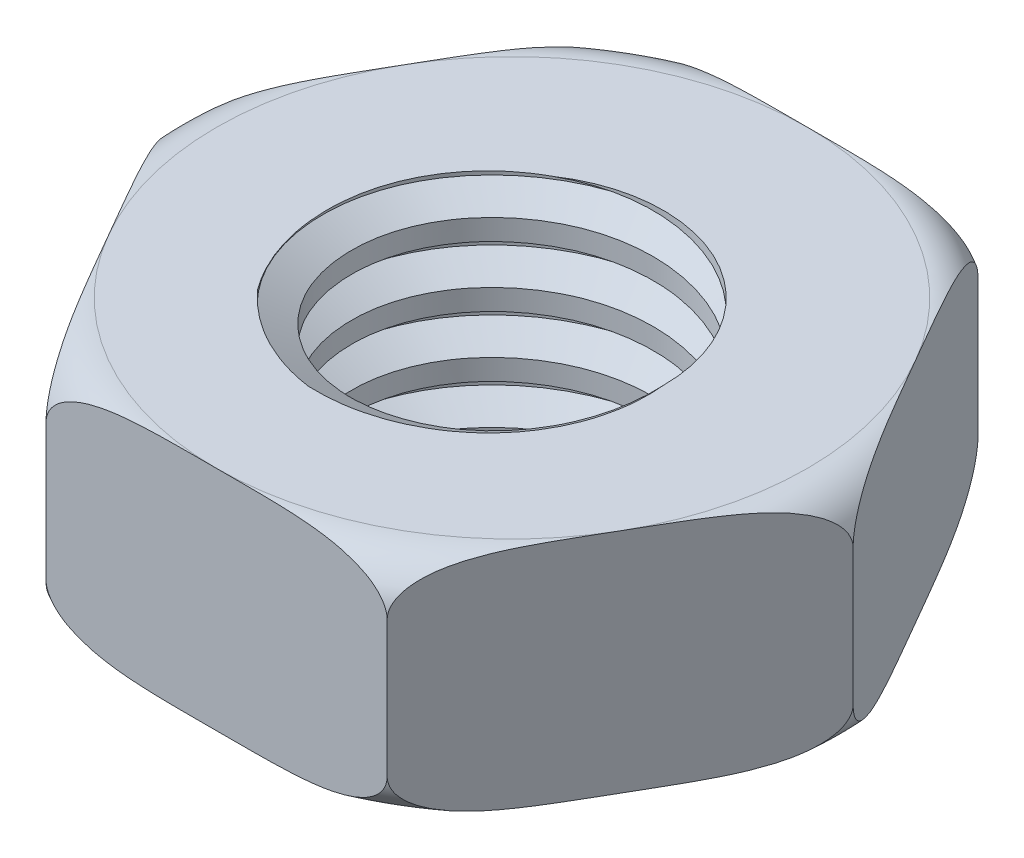
SolidWorks part; units mm, degrees
ref_plane "Front Plane" through (0, 0, 0) normal (0, 0, 1) x (1, 0, 0)
ref_plane "Top Plane" through (0, 0, 0) normal (0, 1, 0) x (1, 0, 0)
ref_plane "Right Plane" through (0, 0, 0) normal (1, 0, 0) x (0, 0, -1)
sketch "Sketch1" plane through (0, 0, 0) normal (0, 1, 0) x (1, 0, 0)
  line L1 (2.2517, 0) -> (1.1258, 1.95)
  line L2 (1.1258, 1.95) -> (-1.1258, 1.95)
  line L3 (-1.1258, 1.95) -> (-2.2517, 0)
  line L4 (-2.2517, 0) -> (-1.1258, -1.95)
  line L5 (-1.1258, -1.95) -> (1.1258, -1.95)
  line L6 (1.1258, -1.95) -> (2.2517, 0)
  circle A0 centre (0, 0) radius 1.95 construction
  circle A1 centre (0, 0) radius 1
  dimension "D2" = 2
  dimension "D1" = 3.9
extrude "Boss-Extrude1" add sketch "Sketch1" along normal mid plane 1.5
sketch "Sketch2" plane through (0, 0, 0) normal (0, 0, 1) x (1, 0, 0)
  line L0 (0, 0.75) -> (0, 0) construction
  line L3 (2.2517, 0.75) -> (2.2517, 0.4483)
  line L4 (1.1258, 0.75) -> (2.2517, 0.75) construction
  line L5 (2.2517, 0.75) -> (2.2517, -0.75) construction
  line L6 (1.1258, -0.75) -> (2.2517, -0.75) construction
  line L7 (1.95, -0.75) -> (2.2517, -0.75)
  line L8 (2.2517, -0.4483) -> (2.2517, -0.75)
  line L9 (2.2517, 0.75) -> (1.95, 0.75)
  line L10 (0, 0.75) -> (1.95, 0.75) construction
  arc A1 (2.2517, -0.4483) -> (1.95, -0.75) centre (1.95, -0.4483) cw
  arc A2 (1.95, 0.75) -> (2.2517, 0.4483) centre (1.95, 0.4483) cw
  point P1 (2.2517, 0.2825)
  dimension "D1" = 1.95
revolve "Cut-Revolve1" cut sketch "Sketch2" angle 360 about L0
thread "Thread1" pitch 0.35 start angle 0, offset 0, length 5, pitch 0.4, diameter 2
ref_plane "Plane1" through (1, 0.75, 0) normal (0, 0, 1) x (1, 0, 0)
sketch "Thread Profile1" plane through (1, 0.75, 0) normal (0, 0, 1) x (1, 0, 0)
  line L0 (0, 0) -> (0, 0.35) construction
  line L1 (0, 0) -> (0.1894, 0.1094)
  line L2 (0.1894, 0.1094) -> (0.1894, 0.1531)
  line L3 (0.1894, 0.1531) -> (0, 0.2625)
  line L4 (0.1894, 0.1312) -> (0, 0.1312) construction
  line L11 (0, 0) -> (0, 0.2625)
  point P2 (0, 0)
  dimension "Pitch" = 0.35
  dimension "Profile_Angle" = 60
  dimension "Profile_Land" = 0.0437
  dimension "Profile_Height" = 0.1894
